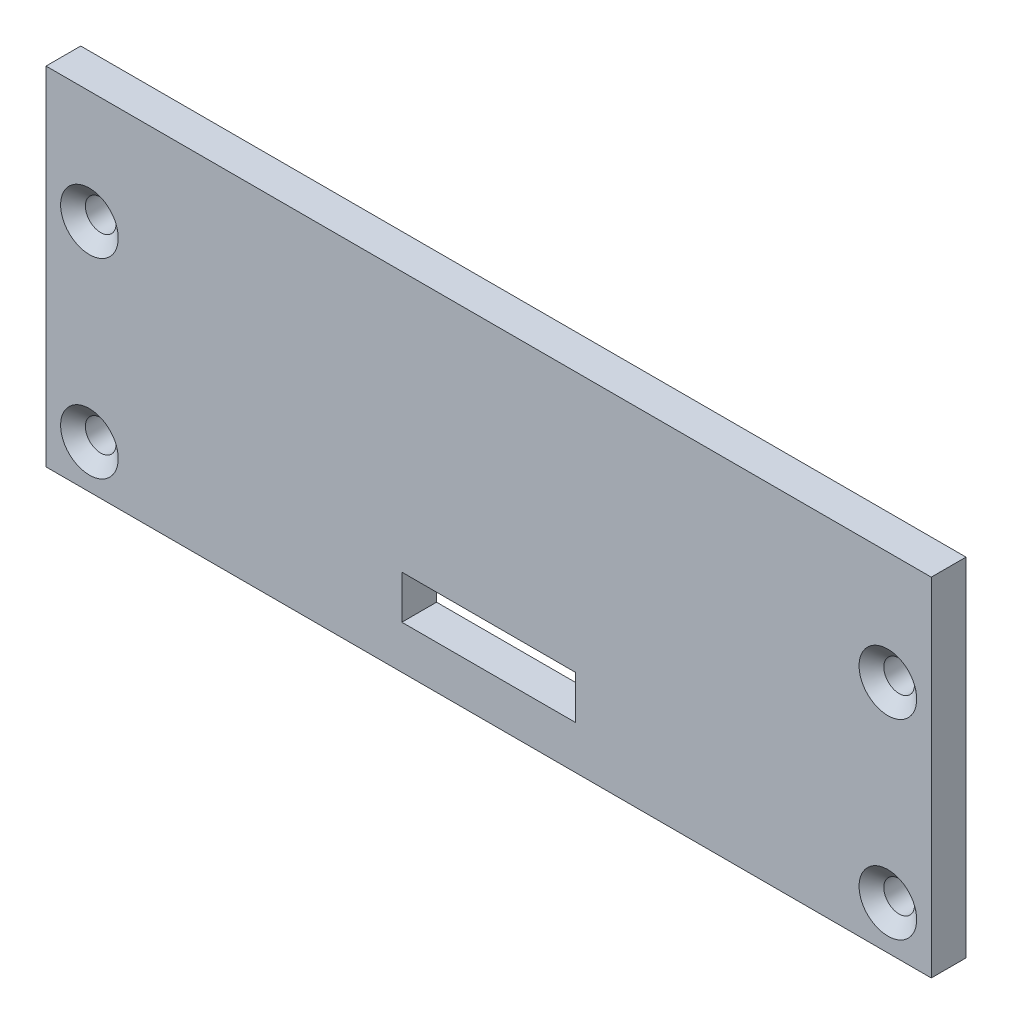
SolidWorks part; units mm, degrees
ref_plane "Front Plane" through (0, 0, 0) normal (0, 0, 1) x (1, 0, 0)
ref_plane "Top Plane" through (0, 0, 0) normal (0, 1, 0) x (1, 0, 0)
ref_plane "Right Plane" through (0, 0, 0) normal (1, 0, 0) x (0, 0, -1)
sketch "Sketch1" plane through (0, 0, 0) normal (0, 0, 1) x (1, 0, 0)
  line L1 (-64.77, -25.4) -> (64.77, -25.4)
  line L2 (-64.77, -25.4) -> (-64.77, 25.4)
  line L3 (-64.77, 25.4) -> (64.77, 25.4)
  line L4 (64.77, -25.4) -> (64.77, 25.4)
  line L5 (0, 25.4) -> (0, -25.4) construction
  line L6 (-64.77, 0) -> (64.77, 0) construction
  point P0 (0, 0)
  dimension "D1" = 129.54
  dimension "D2" = 50.8
extrude "Boss-Extrude1" add sketch "Sketch1" along normal blind 5.08
hole_wizard "CSK for #8 Flat Head Machine Screw (100)1" positions "Sketch4" profile "Sketch3" countersink size "#8" standard "ANSI Inch" end condition through all
sketch "Sketch4" plane through (0, 0, 5.08) normal (0, 0, 1) x (1, 0, 0)
  line L0 (64.77, 25.4) -> (-64.77, 25.4) construction
  line L1 (-64.77, 25.4) -> (-64.77, -25.4) construction
  line L2 (-64.77, -25.4) -> (64.77, -25.4) construction
  line L3 (64.77, -25.4) -> (64.77, 25.4) construction
  point P0 (-58.42, 8.89)
  point P2 (-58.42, -19.05)
  point P4 (58.42, -19.05)
  point P6 (58.42, 8.89)
  dimension "D1" = 16.51
  dimension "D2" = 6.35
  dimension "D3" = 6.35
  dimension "D4" = 6.35
sketch "Sketch3" plane through (-58.42, 8.89, 5.08) normal (1, 0, 0) x (0, -1, 0)
  line L0 (0, 0) -> (0, 5.08)
  line L1 (0, 5.08) -> (2.2479, 5.08)
  line L2 (2.2479, 5.08) -> (2.2479, 1.6518)
  line L3 (2.2479, 1.6518) -> (4.2164, 0)
  line L5 (4.2164, 0) -> (0, 0)
  line L6 (-2.2479, 1.6518) -> (-4.2164, 0) construction
  line L11 (0, -6.35) -> (0, 107.95) construction
  dimension "Thru Hole Dia." = 4.4958
  dimension "Thru Hole Depth" = 5.08
  dimension "Near C'Sink Dia." = 8.4328
  dimension "Near C'Sink Angle" = 100
sketch "Sketch5" plane through (0, 0, 5.08) normal (0, 0, 1) x (1, 0, 0)
  line L0 (-64.77, -25.4) -> (64.77, -25.4) construction
  line L1 (-12.7, -19.05) -> (12.7, -19.05)
  line L2 (-12.7, -19.05) -> (-12.7, -12.7)
  line L3 (-12.7, -12.7) -> (12.7, -12.7)
  line L4 (12.7, -19.05) -> (12.7, -12.7)
  line L5 (0, -12.7) -> (0, -19.05) construction
  line L6 (-12.7, -15.875) -> (12.7, -15.875) construction
  point P0 (0, -15.875)
  dimension "D1" = 6.35
  dimension "D2" = 25.4
  dimension "D3" = 6.35
extrude "Cut-Extrude1" cut sketch "Sketch5" against normal through all
